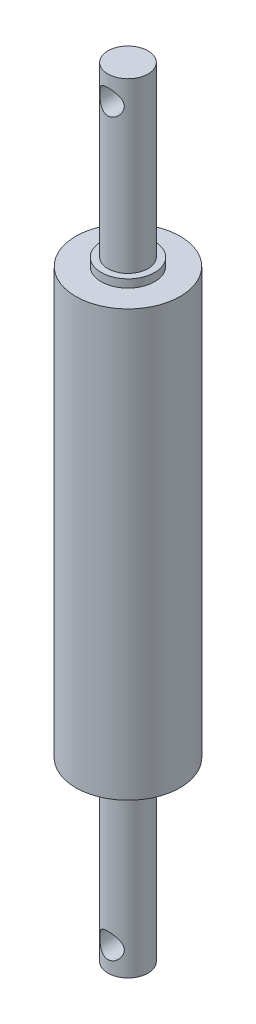
SolidWorks part; units mm, degrees
material "PLA"
ref_plane "Front Plane" through (0, 0, 0) normal (0, 0, 1) x (1, 0, 0)
ref_plane "Top Plane" through (0, 0, 0) normal (0, 1, 0) x (1, 0, 0)
ref_plane "Right Plane" through (0, 0, 0) normal (1, 0, 0) x (0, 0, -1)
sketch "Sketch1" plane through (0, 0, 0) normal (0, 1, 0) x (1, 0, 0)
  circle A0 centre (0, 0) radius 13
  dimension "D1" = 26
extrude "Boss-Extrude1" add sketch "Sketch1" along normal blind 53 and the other way blind 53
sketch "Sketch2" plane through (0, 53, 0) normal (0, 1, 0) x (1, 0, 0)
  circle A0 centre (0, 0) radius 6.65
  dimension "D1" = 13.3
extrude "Boss-Extrude2" add sketch "Sketch2" along normal blind 2
sketch "Sketch3" plane through (0, 55, 0) normal (0, 1, 0) x (1, 0, 0)
  circle A0 centre (0, 0) radius 5
  dimension "D1" = 10
extrude "Boss-Extrude3" add sketch "Sketch3" along normal blind 42
mirror "Mirror1" about plane through (0, 0, 0) normal (0, 1, 0) of "Boss-Extrude3", "Boss-Extrude2"
ref_axis "Axis1" through (0, -53, 0) along (0, 1, 0)
sketch "Sketch4" plane through (0, 0, 0) normal (0, 0, 1) x (1, 0, 0)
  line L0 (0, 97) -> (0, 91) construction
  line L1 (5, 97) -> (-5, 97) construction
  circle A0 centre (0, 91) radius 3.05
  dimension "D2" = 6.1
  dimension "D1" = 6
extrude "Cut-Extrude1" cut sketch "Sketch4" against normal through all and the other way through all
mirror "Mirror2" about plane through (0, 0, 0) normal (0, 1, 0) of "Cut-Extrude1"
ref_plane "Plane1" through (13, 0, 0) normal (1, 0, 0) x (0, 0, -1)
sketch "Sketch5" plane through (13, 0, 0) normal (1, 0, 0) x (0, 0, -1)
  line L0 (13, 53) -> (-13, 53) construction
  line L1 (-1, -53) -> (1, -53)
  line L2 (-1, -53) -> (-1, 53)
  line L3 (-1, 53) -> (1, 53)
  line L4 (1, -53) -> (1, 53)
  line L5 (-1, -53) -> (1, 53) construction
  line L6 (-1, 53) -> (1, -53) construction
  point P0 (0, 0)
  dimension "D1" = 2
extrude "Boss-Extrude4" [suppressed] add sketch "Sketch5" along normal blind 1 and the other way blind 1
